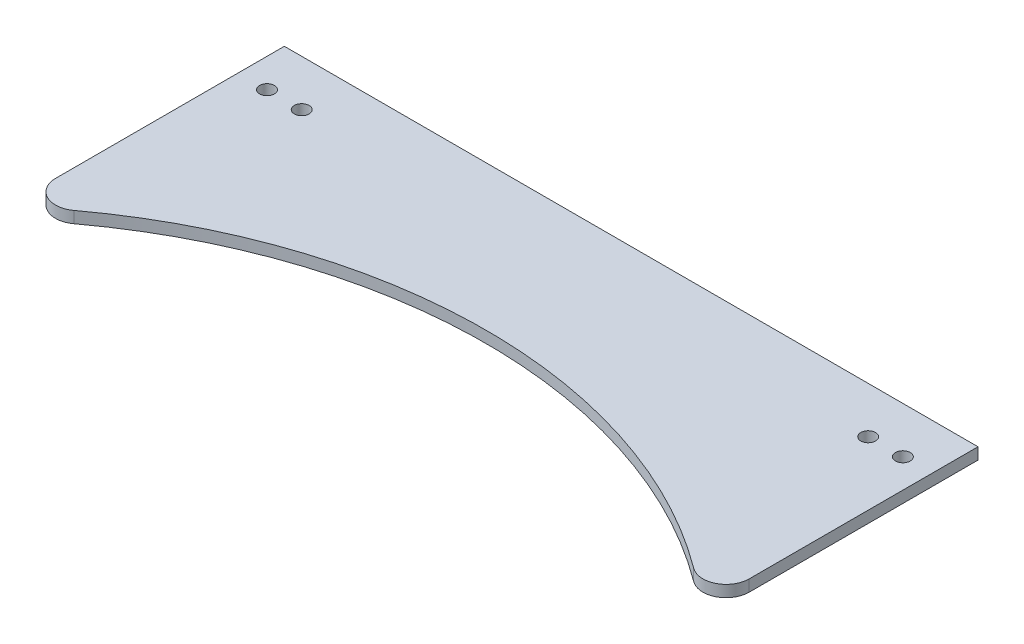
SolidWorks part; units mm, degrees
ref_plane "Front Plane" through (0, 0, 0) normal (0, 0, 1) x (1, 0, 0)
ref_plane "Top Plane" through (0, 0, 0) normal (0, 1, 0) x (1, 0, 0)
ref_plane "Right Plane" through (0, 0, 0) normal (1, 0, 0) x (0, 0, -1)
sketch "Sketch1" plane through (0, 0, 0) normal (0, 1, 0) x (1, 0, 0)
  line L0 (0, 0) -> (0, 76.2)
  line L1 (0, 76.2) -> (190.5, 76.2)
  line L2 (190.5, 76.2) -> (190.5, 0)
  arc A0 (0, 0) -> (190.5, 0) centre (95.25, -106.4927) cw
  dimension "D3" = 142.875
  dimension "D1" = 76.2
  dimension "D2" = 190.5
extrude "Boss-Extrude1" add sketch "Sketch1" along normal blind 3.175
sketch "Sketch3" plane through (0, 0, 0) normal (0, -1, 0) x (1, 0, 0)
  circle A0 centre (17.4625, -63.5) radius 2.032 construction
  circle A1 centre (7.9375, -63.5) radius 2.032 construction
  circle A2 centre (182.5625, -63.5) radius 2.032 construction
  circle A3 centre (173.0375, -63.5) radius 2.032 construction
  circle A4 centre (17.4625, -63.5) radius 2.032
  circle A5 centre (7.9375, -63.5) radius 2.032
  circle A6 centre (182.5625, -63.5) radius 2.032
  circle A7 centre (173.0375, -63.5) radius 2.032
extrude "Cut-Extrude1" cut sketch "Sketch3" against normal through all
fillet "Fillet1" radius 6.35 2 edges at (0, 1.5875, 0) (190.5, 1.5875, 0)
